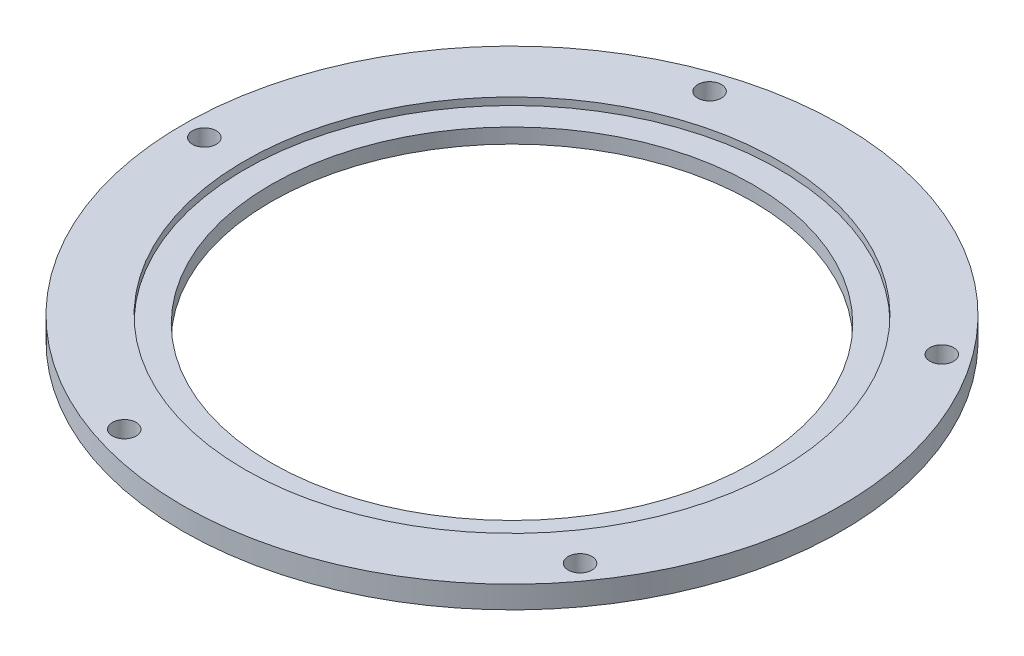
SolidWorks part; units mm, degrees
ref_plane "Front Plane" through (0, 0, 0) normal (0, 0, 1) x (1, 0, 0)
ref_plane "Top Plane" through (0, 0, 0) normal (0, 1, 0) x (1, 0, 0)
ref_plane "Right Plane" through (0, 0, 0) normal (1, 0, 0) x (0, 0, -1)
sketch "Sketch1" plane through (0, 0, 0) normal (0, 1, 0) x (1, 0, 0)
  circle A0 centre (0, 0) radius 44.45
  circle A1 centre (0, 0) radius 36.05
  circle A2 centre (0, 0) radius 32.5
  dimension "D1" = 88.9
  dimension "D2" = 72.1
  dimension "D3" = 65
extrude "Boss-Extrude1" add sketch "Sketch1" along normal blind 3 contours A0 A1 region at (-43.1928, 0, 0)
extrude "Boss-Extrude2" add sketch "Sketch1<3>" along normal blind 2 contours A1 A2 region at (-35.0304, 0, 0)
sketch "Sketch1<3>" plane through (0, 0, 0) normal (0, 1, 0) x (1, 0, 0) same geometry as "Sketch1"
hole_wizard "M3 Clearance Hole1" positions "Sketch2" profile "Sketch3" hole size "M3" standard "ANSI Metric" end condition through all
sketch "Sketch2" plane through (0, 3, 0) normal (0, 1, 0) x (1, 0, 0)
  line L1 (0, 0) -> (-41.5, 0) construction
  point P4 (-41.5, 0)
  dimension "D1" = 41.5
sketch "Sketch3" plane through (-41.5, 3, 0) normal (1, 0, 0) x (0, 0, 1)
  line L0 (0, 0) -> (0, 3)
  line L1 (0, 3) -> (1.6, 3)
  line L2 (1.6, 3) -> (1.6, 0)
  line L5 (1.6, 0) -> (0, 0)
  line L11 (0, -6.35) -> (0, 107.95) construction
  dimension "Thru Hole Dia." = 3.2
  dimension "Thru Hole Depth" = 3
pattern_circular "CirPattern1" count 5 over 360 about axis through (0, 3, 0) along (0, -1, 0) of "M3 Clearance Hole1" reverse direction yes
equation "\"Ratio\"= 15"
equation "\"Hull Diameter\"= 3.5in"
equation "\"Fixed Ring Diameter\"= 76"
equation "\"Fixed Pin Diameter\"= 6"
equation "\"Output Ring Diameter\"= 40"
equation "\"Output Pin Diameter\"= 6"
equation "\"Disk Bearing Inner Diameter\"= 9"
equation "\"Disk Bearing Outer Diameter\"= 17"
equation "\"Disk Bearing Height\"= 5"
equation "\"Shaft Bearing Inner Diameter\"= 15"
equation "\"Shaft Bearing Outer Diameter\"= 21"
equation "\"Shaft Bearing Height\"= 4"
equation "\"Eccentricity\"= 1.5"
equation "\"Disk Height\"= 8"
equation "\"Disk Spacing\"= 5"
equation "\"Hull Height\"= 40"
equation "\"Shaft End Bearing Inner Diameter\"= 12"
equation "\"Shaft End Bearing Outer Diameter\"= 18"
equation "\"Shaft End Bearing Height\"= 4"
equation "\"Output Bearing Inner Diameter\"= 55"
equation "\"Output Bearing Outer Diameter\"= 72"
equation "\"Outer Bearing Height\"= 9"
equation "\"D1@Sketch1\"=\"Hull Diameter\""
equation "\"D2@Sketch1\"=\"Output Bearing Outer Diameter\"+0.1"
equation "\"D3@Sketch1\"=\"Output Bearing Inner Diameter\"+10"
